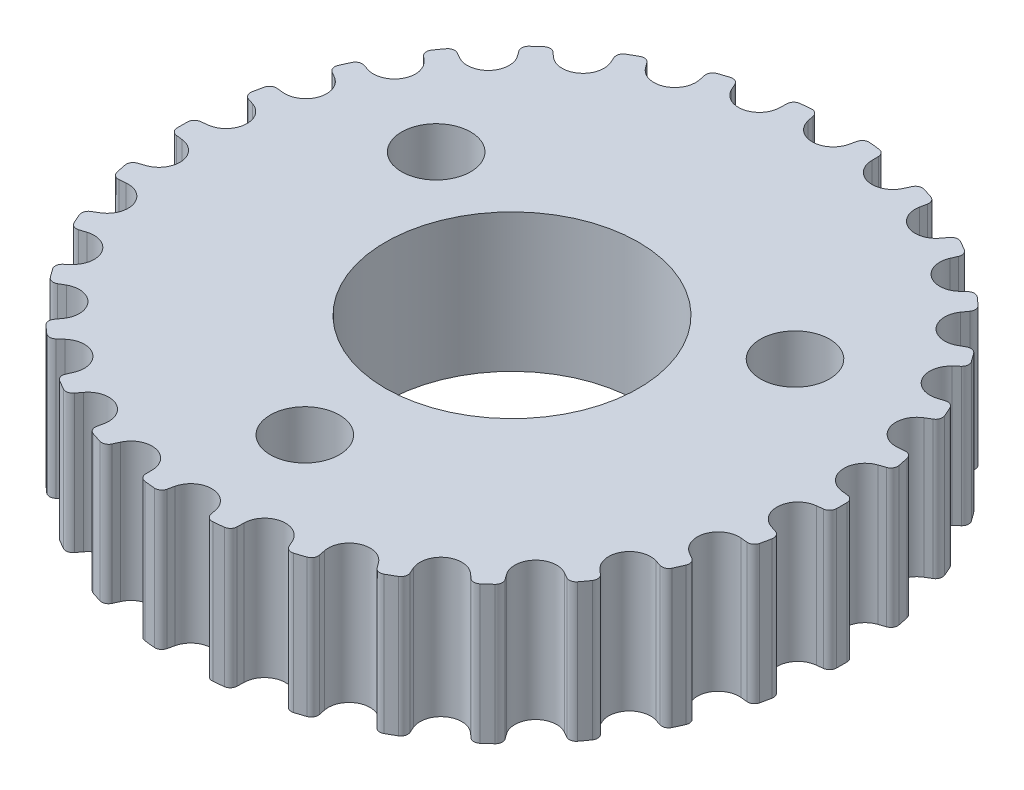
SolidWorks part; units mm, degrees
material "Acrylic (Medium-high impact)"
ref_plane "Front Plane" through (0, 0, 0) normal (0, 0, 1) x (1, 0, 0)
ref_plane "Top Plane" through (0, 0, 0) normal (0, 1, 0) x (1, 0, 0)
ref_plane "Right Plane" through (0, 0, 0) normal (1, 0, 0) x (0, 0, -1)
sketch "Sketch1" plane through (0, 0, 0) normal (0, 1, 0) x (1, 0, 0)
  circle A0 centre (0, 0) radius 14.3239
  dimension "D1" = 28.6479
extrude "Boss-Extrude1" add sketch "Sketch1" along normal blind 6
sketch "Sketch2" plane through (0, 6, 0) normal (0, 1, 0) x (1, 0, 0)
  line L0 (0, 0) -> (0, 14.3239) construction
  line L1 (-0.8883, 13.7564) -> (-0.95, 14.0339)
  line L2 (-2.9781, 14.0109) -> (-2.9781, 14.3239)
  line L3 (-2.9781, 14.3239) -> (2.9781, 14.3239)
  line L4 (0.8883, 13.7564) -> (0.95, 14.0339)
  line L5 (2.9781, 14.0109) -> (2.9781, 14.3239)
  circle A0 centre (0, 0) radius 14.3239 construction
  arc A1 (0.8883, 13.7564) -> (-0.8883, 13.7564) centre (0, 13.9539) cw
  arc A2 (-0.95, 14.0339) -> (-1.2694, 14.2676) centre (-1.2428, 13.9688) ccw
  arc A4 (0.95, 14.0339) -> (1.2694, 14.2676) centre (1.2428, 13.9688) cw
  arc A5 (-1.2694, 14.2676) -> (-2.9781, 14.0109) centre (0, 0) ccw
  arc A6 (1.2694, 14.2676) -> (2.9781, 14.0109) centre (0, 0) cw
  circle A8 centre (0, 0) radius 14.3239 construction
  point P11 (0, 14.3239)
  point P19 (0, 13.0439)
  dimension "D3" = 0.3
  dimension "D5" = 0.91
  dimension "D2" = 0.95
  dimension "D4" = 1.28
  dimension "D6" = 12
extrude "Cut-Extrude1" cut sketch "Sketch2" against normal through all
pattern_circular "CirPattern1" count 30 over 360 about axis through (0, 6, 0) along (0, -1, 0) of "Cut-Extrude1"
sketch "Sketch3" plane through (0, 0, 0) normal (0, -1, 0) x (1, 0, 0)
  circle A0 centre (0, 0) radius 5.5
  dimension "D1" = 11
extrude "Cut-Extrude2" cut sketch "Sketch3" against normal through all
sketch "Sketch4" plane through (0, 0, 0) normal (0, -1, 0) x (1, 0, 0)
  line L0 (0, 0) -> (0, 9) construction
  circle A0 centre (0, 9) radius 1.5
  circle A1 centre (7.7942, -4.5) radius 1.5
  circle A2 centre (-7.7942, -4.5) radius 1.5
  point P14 (0, 0)
  dimension "D1" = 3
  dimension "D2" = 9
  dimension "D3" = 3
extrude "Cut-Extrude3" cut sketch "Sketch4" against normal through all
sketch "Sketch5" plane through (0, 0, 0) normal (0, -1, 0) x (1, 0, 0)
  line L60 (8.7383, -10.682) -> (8.9513, -10.8702)
  line L61 (8.7383, -10.682) -> (8.9513, -10.8702)
  line L62 (9.875, -10.0385) -> (9.7101, -9.807)
  line L63 (9.875, -10.0385) -> (9.7101, -9.807)
  line L64 (12.5987, 6.2896) -> (12.3276, 6.2043)
  line L65 (12.5987, 6.2896) -> (12.3276, 6.2043)
  line L66 (11.5369, 7.5738) -> (11.7463, 7.766)
  line L67 (11.5369, 7.5738) -> (11.7463, 7.766)
  line L68 (-3.638, 13.3126) -> (-3.7561, 13.5712)
  line L69 (-3.638, 13.3126) -> (-3.7561, 13.5712)
  line L70 (-4.9382, 13.1871) -> (-4.8817, 12.9085)
  line L71 (-4.9382, 13.1871) -> (-4.8817, 12.9085)
  line L72 (-11.7463, 7.766) -> (-11.5369, 7.5738)
  line L73 (-11.7463, 7.766) -> (-11.5369, 7.5738)
  line L74 (-12.3276, 6.2043) -> (-12.5987, 6.2896)
  line L75 (-12.3276, 6.2043) -> (-12.5987, 6.2896)
  line L76 (-13.1043, 5.1541) -> (-12.8594, 5.0097)
  line L77 (-13.1043, 5.1541) -> (-12.8594, 5.0097)
  line L78 (-13.3481, 3.5057) -> (-13.6311, 3.5327)
  line L79 (-13.3481, 3.5057) -> (-13.6311, 3.5327)
  line L80 (-13.8895, 2.3169) -> (-13.62, 2.2266)
  line L81 (-13.8895, 2.3169) -> (-13.62, 2.2266)
  line L82 (-13.7853, 0.6538) -> (-14.0677, 0.6215)
  line L83 (-13.7853, 0.6538) -> (-14.0677, 0.6215)
  line L84 (-14.0677, -0.6215) -> (-13.7853, -0.6538)
  line L85 (-14.0677, -0.6215) -> (-13.7853, -0.6538)
  line L86 (-13.62, -2.2266) -> (-13.8895, -2.3169)
  line L87 (-13.62, -2.2266) -> (-13.8895, -2.3169)
  line L88 (-13.6311, -3.5327) -> (-13.3481, -3.5057)
  line L89 (-13.6311, -3.5327) -> (-13.3481, -3.5057)
  line L90 (-12.8594, -5.0097) -> (-13.1043, -5.1541)
  line L91 (-12.8594, -5.0097) -> (-13.1043, -5.1541)
  line L92 (-12.5987, -6.2896) -> (-12.3276, -6.2043)
  line L93 (-12.5987, -6.2896) -> (-12.3276, -6.2043)
  line L94 (-11.5369, -7.5738) -> (-11.7463, -7.766)
  line L95 (-11.5369, -7.5738) -> (-11.7463, -7.766)
  line L96 (-11.0157, -8.7716) -> (-10.7682, -8.6318)
  line L97 (-11.0157, -8.7716) -> (-10.7682, -8.6318)
  line L98 (-9.7101, -9.807) -> (-9.875, -10.0385)
  line L99 (-9.7101, -9.807) -> (-9.875, -10.0385)
  line L100 (-8.9513, -10.8702) -> (-8.7383, -10.682)
  line L101 (-8.9513, -10.8702) -> (-8.7383, -10.682)
  line L102 (-7.4589, -11.6115) -> (-7.5721, -11.8722)
  line L103 (-7.4589, -11.6115) -> (-7.5721, -11.8722)
  line L104 (-6.4956, -12.4937) -> (-6.3264, -12.2653)
  line L105 (-6.4956, -12.4937) -> (-6.3264, -12.2653)
  line L106 (-4.8817, -12.9085) -> (-4.9382, -13.1871)
  line L107 (-4.8817, -12.9085) -> (-4.9382, -13.1871)
  line L108 (-3.7561, -13.5712) -> (-3.638, -13.3126)
  line L109 (-3.7561, -13.5712) -> (-3.638, -13.3126)
  line L110 (-2.0912, -13.6414) -> (-2.0886, -13.9257)
  line L111 (-2.0912, -13.6414) -> (-2.0886, -13.9257)
  line L120 (6.3264, -12.2653) -> (6.4956, -12.4937)
  line L121 (7.5721, -11.8722) -> (7.4589, -11.6115)
  line L124 (10.7682, -8.6318) -> (11.0157, -8.7716)
  line L125 (11.7463, -7.766) -> (11.5369, -7.5738)
  line L126 (12.3276, -6.2043) -> (12.5987, -6.2896)
  line L127 (13.1043, -5.1541) -> (12.8594, -5.0097)
  line L128 (13.3481, -3.5057) -> (13.6311, -3.5327)
  line L129 (13.8895, -2.3169) -> (13.62, -2.2266)
  line L130 (13.7853, -0.6538) -> (14.0677, -0.6215)
  line L131 (14.0677, 0.6215) -> (13.7853, 0.6538)
  line L132 (13.62, 2.2266) -> (13.8895, 2.3169)
  line L133 (13.6311, 3.5327) -> (13.3481, 3.5057)
  line L134 (12.8594, 5.0097) -> (13.1043, 5.1541)
  line L137 (11.0157, 8.7716) -> (10.7682, 8.6318)
  line L138 (9.7101, 9.807) -> (9.875, 10.0385)
  line L139 (8.9513, 10.8702) -> (8.7383, 10.682)
  line L140 (7.4589, 11.6115) -> (7.5721, 11.8722)
  line L141 (6.4956, 12.4937) -> (6.3264, 12.2653)
  line L142 (4.8817, 12.9085) -> (4.9382, 13.1871)
  line L143 (3.7561, 13.5712) -> (3.638, 13.3126)
  line L144 (2.0912, 13.6414) -> (2.0886, 13.9257)
  line L145 (0.8524, 14.0556) -> (0.7907, 13.7781)
  line L146 (-0.7907, 13.7781) -> (-0.8524, 14.0556)
  line L147 (-2.0886, 13.9257) -> (-2.0912, 13.6414)
  line L150 (-6.3264, 12.2653) -> (-6.4956, 12.4937)
  line L151 (-7.5721, 11.8722) -> (-7.4589, 11.6115)
  line L152 (-8.7383, 10.682) -> (-8.9513, 10.8702)
  line L153 (-9.875, 10.0385) -> (-9.7101, 9.807)
  line L154 (-10.7682, 8.6318) -> (-11.0157, 8.7716)
  line L175 (-0.8524, -14.0556) -> (-0.7907, -13.7781)
  line L176 (0.7907, -13.7781) -> (0.8524, -14.0556)
  line L177 (2.0886, -13.9257) -> (2.0912, -13.6414)
  line L178 (3.638, -13.3126) -> (3.7561, -13.5712)
  line L179 (4.9382, -13.1871) -> (4.8817, -12.9085)
  line L180 (6.3264, -12.2653) -> (6.4956, -12.4937)
  line L181 (7.5721, -11.8722) -> (7.4589, -11.6115)
  line L184 (10.7682, -8.6318) -> (11.0157, -8.7716)
  line L185 (11.7463, -7.766) -> (11.5369, -7.5738)
  line L186 (12.3276, -6.2043) -> (12.5987, -6.2896)
  line L187 (13.1043, -5.1541) -> (12.8594, -5.0097)
  line L188 (13.3481, -3.5057) -> (13.6311, -3.5327)
  line L189 (13.8895, -2.3169) -> (13.62, -2.2266)
  line L190 (13.7853, -0.6538) -> (14.0677, -0.6215)
  line L191 (14.0677, 0.6215) -> (13.7853, 0.6538)
  line L192 (13.62, 2.2266) -> (13.8895, 2.3169)
  line L193 (13.6311, 3.5327) -> (13.3481, 3.5057)
  line L194 (12.8594, 5.0097) -> (13.1043, 5.1541)
  line L197 (11.0157, 8.7716) -> (10.7682, 8.6318)
  line L198 (9.7101, 9.807) -> (9.875, 10.0385)
  line L199 (8.9513, 10.8702) -> (8.7383, 10.682)
  line L200 (7.4589, 11.6115) -> (7.5721, 11.8722)
  line L201 (6.4956, 12.4937) -> (6.3264, 12.2653)
  line L202 (4.8817, 12.9085) -> (4.9382, 13.1871)
  line L203 (3.7561, 13.5712) -> (3.638, 13.3126)
  line L204 (2.0912, 13.6414) -> (2.0886, 13.9257)
  line L205 (0.8524, 14.0556) -> (0.7907, 13.7781)
  line L206 (-0.7907, 13.7781) -> (-0.8524, 14.0556)
  line L207 (-2.0886, 13.9257) -> (-2.0912, 13.6414)
  line L210 (-6.3264, 12.2653) -> (-6.4956, 12.4937)
  line L211 (-7.5721, 11.8722) -> (-7.4589, 11.6115)
  line L212 (-8.7383, 10.682) -> (-8.9513, 10.8702)
  line L213 (-9.875, 10.0385) -> (-9.7101, 9.807)
  line L214 (-10.7682, 8.6318) -> (-11.0157, 8.7716)
  line L235 (-0.8524, -14.0556) -> (-0.7907, -13.7781)
  line L236 (0.7907, -13.7781) -> (0.8524, -14.0556)
  line L237 (2.0886, -13.9257) -> (2.0912, -13.6414)
  line L238 (3.638, -13.3126) -> (3.7561, -13.5712)
  line L239 (4.9382, -13.1871) -> (4.8817, -12.9085)
  arc A76 (8.9513, -10.8702) -> (9.479, -10.8719) centre (9.2161, -10.5704) ccw
  arc A77 (8.9513, -10.8702) -> (9.479, -10.8719) centre (9.2161, -10.5704) ccw
  arc A78 (9.479, -10.8719) -> (9.8216, -10.5635) centre (0, 0) ccw
  arc A79 (9.479, -10.8719) -> (9.8216, -10.5635) centre (0, 0) ccw
  arc A80 (9.8216, -10.5635) -> (9.875, -10.0385) centre (9.5492, -10.2705) ccw
  arc A81 (9.8216, -10.5635) -> (9.875, -10.0385) centre (9.5492, -10.2705) ccw
  circle A120 centre (0, 0) radius 13.0439
  arc A121 (-0.8883, 13.7564) -> (0.8883, 13.7564) centre (0, 13.9539) ccw construction
  arc A128 (11.5369, 7.5738) -> (12.3276, 6.2043) centre (12.0845, 6.977) ccw
  arc A129 (11.5369, 7.5738) -> (12.3276, 6.2043) centre (12.0845, 6.977) ccw
  arc A130 (-3.7561, 13.5712) -> (-4.2375, 13.7875) centre (-4.12, 13.4051) ccw
  arc A131 (-3.7561, 13.5712) -> (-4.2375, 13.7875) centre (-4.12, 13.4051) ccw
  arc A132 (-4.2375, 13.7875) -> (-4.6759, 13.645) centre (0, 0) ccw
  arc A133 (-4.2375, 13.7875) -> (-4.6759, 13.645) centre (0, 0) ccw
  arc A134 (-4.6759, 13.645) -> (-4.9382, 13.1871) centre (-4.5462, 13.2666) ccw
  arc A135 (-4.6759, 13.645) -> (-4.9382, 13.1871) centre (-4.5462, 13.2666) ccw
  arc A136 (-11.8032, 8.2906) -> (-11.7463, 7.766) centre (-11.4759, 8.0607) ccw
  arc A137 (-11.8032, 8.2906) -> (-11.7463, 7.766) centre (-11.4759, 8.0607) ccw
  arc A138 (-12.3276, 6.2043) -> (-11.5369, 7.5738) centre (-12.0845, 6.977) ccw
  arc A139 (-12.3276, 6.2043) -> (-11.5369, 7.5738) centre (-12.0845, 6.977) ccw
  arc A140 (-12.5987, 6.2896) -> (-13.0815, 6.0766) centre (-12.7187, 5.908) ccw
  arc A141 (-12.5987, 6.2896) -> (-13.0815, 6.0766) centre (-12.7187, 5.908) ccw
  arc A142 (-13.0815, 6.0766) -> (-13.269, 5.6554) centre (0, 0) ccw
  arc A143 (-13.0815, 6.0766) -> (-13.269, 5.6554) centre (0, 0) ccw
  arc A144 (-13.269, 5.6554) -> (-13.1043, 5.1541) centre (-12.901, 5.4986) ccw
  arc A145 (-13.269, 5.6554) -> (-13.1043, 5.1541) centre (-12.901, 5.4986) ccw
  arc A146 (-13.3481, 3.5057) -> (-12.8594, 5.0097) centre (-13.271, 4.312) ccw
  arc A147 (-13.3481, 3.5057) -> (-12.8594, 5.0097) centre (-13.271, 4.312) ccw
  arc A148 (-13.6311, 3.5327) -> (-14.059, 3.224) centre (-13.6691, 3.1346) ccw
  arc A149 (-13.6311, 3.5327) -> (-14.059, 3.224) centre (-13.6691, 3.1346) ccw
  arc A150 (-14.059, 3.224) -> (-14.1549, 2.7731) centre (0, 0) ccw
  arc A151 (-14.059, 3.224) -> (-14.1549, 2.7731) centre (0, 0) ccw
  arc A152 (-14.1549, 2.7731) -> (-13.8895, 2.3169) centre (-13.7623, 2.6962) ccw
  arc A153 (-14.1549, 2.7731) -> (-13.8895, 2.3169) centre (-13.7623, 2.6962) ccw
  arc A154 (-13.7853, 0.6538) -> (-13.62, 2.2266) centre (-13.8775, 1.4586) ccw
  arc A155 (-13.7853, 0.6538) -> (-13.62, 2.2266) centre (-13.8775, 1.4586) ccw
  arc A156 (-14.0677, 0.6215) -> (-14.4221, 0.2305) centre (-14.0222, 0.2241) ccw
  arc A157 (-14.0677, 0.6215) -> (-14.4221, 0.2305) centre (-14.0222, 0.2241) ccw
  arc A158 (-14.4221, 0.2305) -> (-14.4221, -0.2305) centre (0, 0) ccw
  arc A159 (-14.4221, 0.2305) -> (-14.4221, -0.2305) centre (0, 0) ccw
  arc A160 (-14.4221, -0.2305) -> (-14.0677, -0.6215) centre (-14.0222, -0.2241) ccw
  arc A161 (-14.4221, -0.2305) -> (-14.0677, -0.6215) centre (-14.0222, -0.2241) ccw
  arc A162 (-13.62, -2.2266) -> (-13.7853, -0.6538) centre (-13.8775, -1.4586) ccw
  arc A163 (-13.62, -2.2266) -> (-13.7853, -0.6538) centre (-13.8775, -1.4586) ccw
  arc A164 (-13.8895, -2.3169) -> (-14.1549, -2.7731) centre (-13.7623, -2.6962) ccw
  arc A165 (-13.8895, -2.3169) -> (-14.1549, -2.7731) centre (-13.7623, -2.6962) ccw
  arc A166 (-14.1549, -2.7731) -> (-14.059, -3.224) centre (0, 0) ccw
  arc A167 (-14.1549, -2.7731) -> (-14.059, -3.224) centre (0, 0) ccw
  arc A168 (-14.059, -3.224) -> (-13.6311, -3.5327) centre (-13.6691, -3.1346) ccw
  arc A169 (-14.059, -3.224) -> (-13.6311, -3.5327) centre (-13.6691, -3.1346) ccw
  arc A170 (-12.8594, -5.0097) -> (-13.3481, -3.5057) centre (-13.271, -4.312) ccw
  arc A171 (-12.8594, -5.0097) -> (-13.3481, -3.5057) centre (-13.271, -4.312) ccw
  arc A172 (-13.1043, -5.1541) -> (-13.269, -5.6554) centre (-12.901, -5.4986) ccw
  arc A173 (-13.1043, -5.1541) -> (-13.269, -5.6554) centre (-12.901, -5.4986) ccw
  arc A174 (-13.269, -5.6554) -> (-13.0815, -6.0766) centre (0, 0) ccw
  arc A175 (-13.269, -5.6554) -> (-13.0815, -6.0766) centre (0, 0) ccw
  arc A176 (-13.0815, -6.0766) -> (-12.5987, -6.2896) centre (-12.7187, -5.908) ccw
  arc A177 (-13.0815, -6.0766) -> (-12.5987, -6.2896) centre (-12.7187, -5.908) ccw
  arc A178 (-11.5369, -7.5738) -> (-12.3276, -6.2043) centre (-12.0845, -6.977) ccw
  arc A179 (-11.5369, -7.5738) -> (-12.3276, -6.2043) centre (-12.0845, -6.977) ccw
  arc A180 (-11.7463, -7.766) -> (-11.8032, -8.2906) centre (-11.4759, -8.0607) ccw
  arc A181 (-11.7463, -7.766) -> (-11.8032, -8.2906) centre (-11.4759, -8.0607) ccw
  arc A182 (-11.8032, -8.2906) -> (-11.5323, -8.6636) centre (0, 0) ccw
  arc A183 (-11.8032, -8.2906) -> (-11.5323, -8.6636) centre (0, 0) ccw
  arc A184 (-11.5323, -8.6636) -> (-11.0157, -8.7716) centre (-11.2124, -8.4233) ccw
  arc A185 (-11.5323, -8.6636) -> (-11.0157, -8.7716) centre (-11.2124, -8.4233) ccw
  arc A186 (-9.7101, -9.807) -> (-10.7682, -8.6318) centre (-10.3698, -9.337) ccw
  arc A187 (-9.7101, -9.807) -> (-10.7682, -8.6318) centre (-10.3698, -9.337) ccw
  arc A188 (-9.875, -10.0385) -> (-9.8216, -10.5635) centre (-9.5492, -10.2705) ccw
  arc A189 (-9.875, -10.0385) -> (-9.8216, -10.5635) centre (-9.5492, -10.2705) ccw
  arc A190 (-9.8216, -10.5635) -> (-9.479, -10.8719) centre (0, 0) ccw
  arc A191 (-9.8216, -10.5635) -> (-9.479, -10.8719) centre (0, 0) ccw
  arc A192 (-9.479, -10.8719) -> (-8.9513, -10.8702) centre (-9.2161, -10.5704) ccw
  arc A193 (-9.479, -10.8719) -> (-8.9513, -10.8702) centre (-9.2161, -10.5704) ccw
  arc A194 (-7.4589, -11.6115) -> (-8.7383, -10.682) centre (-8.2019, -11.289) ccw
  arc A195 (-7.4589, -11.6115) -> (-8.7383, -10.682) centre (-8.2019, -11.289) ccw
  arc A196 (-7.5721, -11.8722) -> (-7.4107, -12.3747) centre (-7.2051, -12.0315) ccw
  arc A197 (-7.5721, -11.8722) -> (-7.4107, -12.3747) centre (-7.2051, -12.0315) ccw
  arc A198 (-7.4107, -12.3747) -> (-7.0114, -12.6052) centre (0, 0) ccw
  arc A199 (-7.4107, -12.3747) -> (-7.0114, -12.6052) centre (0, 0) ccw
  arc A200 (-7.0114, -12.6052) -> (-6.4956, -12.4937) centre (-6.817, -12.2556) ccw
  arc A201 (-7.0114, -12.6052) -> (-6.4956, -12.4937) centre (-6.817, -12.2556) ccw
  arc A202 (-4.8817, -12.9085) -> (-6.3264, -12.2653) centre (-5.6756, -12.7476) ccw
  arc A203 (-4.8817, -12.9085) -> (-6.3264, -12.2653) centre (-5.6756, -12.7476) ccw
  arc A204 (-4.9382, -13.1871) -> (-4.6759, -13.645) centre (-4.5462, -13.2666) ccw
  arc A205 (-4.9382, -13.1871) -> (-4.6759, -13.645) centre (-4.5462, -13.2666) ccw
  arc A206 (-4.6759, -13.645) -> (-4.2375, -13.7875) centre (0, 0) ccw
  arc A207 (-4.6759, -13.645) -> (-4.2375, -13.7875) centre (0, 0) ccw
  arc A208 (-4.2375, -13.7875) -> (-3.7561, -13.5712) centre (-4.12, -13.4051) ccw
  arc A209 (-4.2375, -13.7875) -> (-3.7561, -13.5712) centre (-4.12, -13.4051) ccw
  arc A210 (-2.0912, -13.6414) -> (-3.638, -13.3126) centre (-2.9012, -13.649) ccw
  arc A211 (-2.0912, -13.6414) -> (-3.638, -13.3126) centre (-2.9012, -13.649) ccw
  arc A212 (-2.0886, -13.9257) -> (-1.7367, -14.319) centre (-1.6886, -13.9219) ccw
  arc A213 (-2.0886, -13.9257) -> (-1.7367, -14.319) centre (-1.6886, -13.9219) ccw
  arc A214 (-1.7367, -14.319) -> (-1.2783, -14.3672) centre (0, 0) ccw
  arc A215 (-1.7367, -14.319) -> (-1.2783, -14.3672) centre (0, 0) ccw
  arc A240 (6.4956, -12.4937) -> (7.0114, -12.6052) centre (6.817, -12.2556) ccw
  arc A241 (7.0114, -12.6052) -> (7.4107, -12.3747) centre (0, 0) ccw
  arc A242 (7.4107, -12.3747) -> (7.5721, -11.8722) centre (7.2051, -12.0315) ccw
  arc A243 (8.7383, -10.682) -> (7.4589, -11.6115) centre (8.2019, -11.289) ccw
  arc A247 (10.7682, -8.6318) -> (9.7101, -9.807) centre (10.3698, -9.337) ccw
  arc A248 (11.0157, -8.7716) -> (11.5323, -8.6636) centre (11.2124, -8.4233) ccw
  arc A249 (11.5323, -8.6636) -> (11.8032, -8.2906) centre (0, 0) ccw
  arc A250 (11.8032, -8.2906) -> (11.7463, -7.766) centre (11.4759, -8.0607) ccw
  arc A251 (12.3276, -6.2043) -> (11.5369, -7.5738) centre (12.0845, -6.977) ccw
  arc A252 (12.5987, -6.2896) -> (13.0815, -6.0766) centre (12.7187, -5.908) ccw
  arc A253 (13.0815, -6.0766) -> (13.269, -5.6554) centre (0, 0) ccw
  arc A254 (13.269, -5.6554) -> (13.1043, -5.1541) centre (12.901, -5.4986) ccw
  arc A255 (13.3481, -3.5057) -> (12.8594, -5.0097) centre (13.271, -4.312) ccw
  arc A256 (13.6311, -3.5327) -> (14.059, -3.224) centre (13.6691, -3.1346) ccw
  arc A257 (14.059, -3.224) -> (14.1549, -2.7731) centre (0, 0) ccw
  arc A258 (14.1549, -2.7731) -> (13.8895, -2.3169) centre (13.7623, -2.6962) ccw
  arc A259 (13.7853, -0.6538) -> (13.62, -2.2266) centre (13.8775, -1.4586) ccw
  arc A260 (14.0677, -0.6215) -> (14.4221, -0.2305) centre (14.0222, -0.2241) ccw
  arc A261 (14.4221, -0.2305) -> (14.4221, 0.2305) centre (0, 0) ccw
  arc A262 (14.4221, 0.2305) -> (14.0677, 0.6215) centre (14.0222, 0.2241) ccw
  arc A263 (13.62, 2.2266) -> (13.7853, 0.6538) centre (13.8775, 1.4586) ccw
  arc A264 (13.8895, 2.3169) -> (14.1549, 2.7731) centre (13.7623, 2.6962) ccw
  arc A265 (14.1549, 2.7731) -> (14.059, 3.224) centre (0, 0) ccw
  arc A266 (14.059, 3.224) -> (13.6311, 3.5327) centre (13.6691, 3.1346) ccw
  arc A267 (12.8594, 5.0097) -> (13.3481, 3.5057) centre (13.271, 4.312) ccw
  arc A268 (13.1043, 5.1541) -> (13.269, 5.6554) centre (12.901, 5.4986) ccw
  arc A269 (13.269, 5.6554) -> (13.0815, 6.0766) centre (0, 0) ccw
  arc A270 (13.0815, 6.0766) -> (12.5987, 6.2896) centre (12.7187, 5.908) ccw
  arc A272 (11.7463, 7.766) -> (11.8032, 8.2906) centre (11.4759, 8.0607) ccw
  arc A273 (11.8032, 8.2906) -> (11.5323, 8.6636) centre (0, 0) ccw
  arc A274 (11.5323, 8.6636) -> (11.0157, 8.7716) centre (11.2124, 8.4233) ccw
  arc A275 (9.7101, 9.807) -> (10.7682, 8.6318) centre (10.3698, 9.337) ccw
  arc A276 (9.875, 10.0385) -> (9.8216, 10.5635) centre (9.5492, 10.2705) ccw
  arc A277 (9.8216, 10.5635) -> (9.479, 10.8719) centre (0, 0) ccw
  arc A278 (9.479, 10.8719) -> (8.9513, 10.8702) centre (9.2161, 10.5704) ccw
  arc A279 (7.4589, 11.6115) -> (8.7383, 10.682) centre (8.2019, 11.289) ccw
  arc A280 (7.5721, 11.8722) -> (7.4107, 12.3747) centre (7.2051, 12.0315) ccw
  arc A281 (7.4107, 12.3747) -> (7.0114, 12.6052) centre (0, 0) ccw
  arc A282 (7.0114, 12.6052) -> (6.4956, 12.4937) centre (6.817, 12.2556) ccw
  arc A283 (4.8817, 12.9085) -> (6.3264, 12.2653) centre (5.6756, 12.7476) ccw
  arc A284 (4.9382, 13.1871) -> (4.6759, 13.645) centre (4.5462, 13.2666) ccw
  arc A285 (4.6759, 13.645) -> (4.2375, 13.7875) centre (0, 0) ccw
  arc A286 (4.2375, 13.7875) -> (3.7561, 13.5712) centre (4.12, 13.4051) ccw
  arc A287 (2.0912, 13.6414) -> (3.638, 13.3126) centre (2.9012, 13.649) ccw
  arc A288 (2.0886, 13.9257) -> (1.7367, 14.319) centre (1.6886, 13.9219) ccw
  arc A289 (1.7367, 14.319) -> (1.2783, 14.3672) centre (0, 0) ccw
  arc A290 (1.2783, 14.3672) -> (0.8524, 14.0556) centre (1.2428, 13.9688) ccw
  arc A291 (-0.7907, 13.7781) -> (0.7907, 13.7781) centre (0, 13.9539) ccw
  arc A292 (-0.8524, 14.0556) -> (-1.2783, 14.3672) centre (-1.2428, 13.9688) ccw
  arc A293 (-1.2783, 14.3672) -> (-1.7367, 14.319) centre (0, 0) ccw
  arc A294 (-1.7367, 14.319) -> (-2.0886, 13.9257) centre (-1.6886, 13.9219) ccw
  arc A295 (-3.638, 13.3126) -> (-2.0912, 13.6414) centre (-2.9012, 13.649) ccw
  arc A299 (-6.3264, 12.2653) -> (-4.8817, 12.9085) centre (-5.6756, 12.7476) ccw
  arc A300 (-6.4956, 12.4937) -> (-7.0114, 12.6052) centre (-6.817, 12.2556) ccw
  arc A301 (-7.0114, 12.6052) -> (-7.4107, 12.3747) centre (0, 0) ccw
  arc A302 (-7.4107, 12.3747) -> (-7.5721, 11.8722) centre (-7.2051, 12.0315) ccw
  arc A303 (-8.7383, 10.682) -> (-7.4589, 11.6115) centre (-8.2019, 11.289) ccw
  arc A304 (-8.9513, 10.8702) -> (-9.479, 10.8719) centre (-9.2161, 10.5704) ccw
  arc A305 (-9.479, 10.8719) -> (-9.8216, 10.5635) centre (0, 0) ccw
  arc A306 (-9.8216, 10.5635) -> (-9.875, 10.0385) centre (-9.5492, 10.2705) ccw
  arc A307 (-10.7682, 8.6318) -> (-9.7101, 9.807) centre (-10.3698, 9.337) ccw
  arc A308 (-11.0157, 8.7716) -> (-11.5323, 8.6636) centre (-11.2124, 8.4233) ccw
  arc A309 (-11.5323, 8.6636) -> (-11.8032, 8.2906) centre (0, 0) ccw
  arc A350 (-1.2783, -14.3672) -> (-0.8524, -14.0556) centre (-1.2428, -13.9688) ccw
  arc A351 (0.7907, -13.7781) -> (-0.7907, -13.7781) centre (0, -13.9539) ccw
  arc A352 (0.8524, -14.0556) -> (1.2783, -14.3672) centre (1.2428, -13.9688) ccw
  arc A353 (1.2783, -14.3672) -> (1.7367, -14.319) centre (0, 0) ccw
  arc A354 (1.7367, -14.319) -> (2.0886, -13.9257) centre (1.6886, -13.9219) ccw
  arc A355 (3.638, -13.3126) -> (2.0912, -13.6414) centre (2.9012, -13.649) ccw
  arc A356 (3.7561, -13.5712) -> (4.2375, -13.7875) centre (4.12, -13.4051) ccw
  arc A357 (4.2375, -13.7875) -> (4.6759, -13.645) centre (0, 0) ccw
  arc A358 (4.6759, -13.645) -> (4.9382, -13.1871) centre (4.5462, -13.2666) ccw
  arc A359 (6.3264, -12.2653) -> (4.8817, -12.9085) centre (5.6756, -12.7476) ccw
  arc A360 (6.4956, -12.4937) -> (7.0114, -12.6052) centre (6.817, -12.2556) ccw
  arc A361 (7.0114, -12.6052) -> (7.4107, -12.3747) centre (0, 0) ccw
  arc A362 (7.4107, -12.3747) -> (7.5721, -11.8722) centre (7.2051, -12.0315) ccw
  arc A363 (8.7383, -10.682) -> (7.4589, -11.6115) centre (8.2019, -11.289) ccw
  arc A367 (10.7682, -8.6318) -> (9.7101, -9.807) centre (10.3698, -9.337) ccw
  arc A368 (11.0157, -8.7716) -> (11.5323, -8.6636) centre (11.2124, -8.4233) ccw
  arc A369 (11.5323, -8.6636) -> (11.8032, -8.2906) centre (0, 0) ccw
  arc A370 (11.8032, -8.2906) -> (11.7463, -7.766) centre (11.4759, -8.0607) ccw
  arc A371 (12.3276, -6.2043) -> (11.5369, -7.5738) centre (12.0845, -6.977) ccw
  arc A372 (12.5987, -6.2896) -> (13.0815, -6.0766) centre (12.7187, -5.908) ccw
  arc A373 (13.0815, -6.0766) -> (13.269, -5.6554) centre (0, 0) ccw
  arc A374 (13.269, -5.6554) -> (13.1043, -5.1541) centre (12.901, -5.4986) ccw
  arc A375 (13.3481, -3.5057) -> (12.8594, -5.0097) centre (13.271, -4.312) ccw
  arc A376 (13.6311, -3.5327) -> (14.059, -3.224) centre (13.6691, -3.1346) ccw
  arc A377 (14.059, -3.224) -> (14.1549, -2.7731) centre (0, 0) ccw
  arc A378 (14.1549, -2.7731) -> (13.8895, -2.3169) centre (13.7623, -2.6962) ccw
  arc A379 (13.7853, -0.6538) -> (13.62, -2.2266) centre (13.8775, -1.4586) ccw
  arc A380 (14.0677, -0.6215) -> (14.4221, -0.2305) centre (14.0222, -0.2241) ccw
  arc A381 (14.4221, -0.2305) -> (14.4221, 0.2305) centre (0, 0) ccw
  arc A382 (14.4221, 0.2305) -> (14.0677, 0.6215) centre (14.0222, 0.2241) ccw
  arc A383 (13.62, 2.2266) -> (13.7853, 0.6538) centre (13.8775, 1.4586) ccw
  arc A384 (13.8895, 2.3169) -> (14.1549, 2.7731) centre (13.7623, 2.6962) ccw
  arc A385 (14.1549, 2.7731) -> (14.059, 3.224) centre (0, 0) ccw
  arc A386 (14.059, 3.224) -> (13.6311, 3.5327) centre (13.6691, 3.1346) ccw
  arc A387 (12.8594, 5.0097) -> (13.3481, 3.5057) centre (13.271, 4.312) ccw
  arc A388 (13.1043, 5.1541) -> (13.269, 5.6554) centre (12.901, 5.4986) ccw
  arc A389 (13.269, 5.6554) -> (13.0815, 6.0766) centre (0, 0) ccw
  arc A390 (13.0815, 6.0766) -> (12.5987, 6.2896) centre (12.7187, 5.908) ccw
  arc A392 (11.7463, 7.766) -> (11.8032, 8.2906) centre (11.4759, 8.0607) ccw
  arc A393 (11.8032, 8.2906) -> (11.5323, 8.6636) centre (0, 0) ccw
  arc A394 (11.5323, 8.6636) -> (11.0157, 8.7716) centre (11.2124, 8.4233) ccw
  arc A395 (9.7101, 9.807) -> (10.7682, 8.6318) centre (10.3698, 9.337) ccw
  arc A396 (9.875, 10.0385) -> (9.8216, 10.5635) centre (9.5492, 10.2705) ccw
  arc A397 (9.8216, 10.5635) -> (9.479, 10.8719) centre (0, 0) ccw
  arc A398 (9.479, 10.8719) -> (8.9513, 10.8702) centre (9.2161, 10.5704) ccw
  arc A399 (7.4589, 11.6115) -> (8.7383, 10.682) centre (8.2019, 11.289) ccw
  arc A400 (7.5721, 11.8722) -> (7.4107, 12.3747) centre (7.2051, 12.0315) ccw
  arc A401 (7.4107, 12.3747) -> (7.0114, 12.6052) centre (0, 0) ccw
  arc A402 (7.0114, 12.6052) -> (6.4956, 12.4937) centre (6.817, 12.2556) ccw
  arc A403 (4.8817, 12.9085) -> (6.3264, 12.2653) centre (5.6756, 12.7476) ccw
  arc A404 (4.9382, 13.1871) -> (4.6759, 13.645) centre (4.5462, 13.2666) ccw
  arc A405 (4.6759, 13.645) -> (4.2375, 13.7875) centre (0, 0) ccw
  arc A406 (4.2375, 13.7875) -> (3.7561, 13.5712) centre (4.12, 13.4051) ccw
  arc A407 (2.0912, 13.6414) -> (3.638, 13.3126) centre (2.9012, 13.649) ccw
  arc A408 (2.0886, 13.9257) -> (1.7367, 14.319) centre (1.6886, 13.9219) ccw
  arc A409 (1.7367, 14.319) -> (1.2783, 14.3672) centre (0, 0) ccw
  arc A410 (1.2783, 14.3672) -> (0.8524, 14.0556) centre (1.2428, 13.9688) ccw
  arc A411 (-0.7907, 13.7781) -> (0.7907, 13.7781) centre (0, 13.9539) ccw
  arc A412 (-0.8524, 14.0556) -> (-1.2783, 14.3672) centre (-1.2428, 13.9688) ccw
  arc A413 (-1.2783, 14.3672) -> (-1.7367, 14.319) centre (0, 0) ccw
  arc A414 (-1.7367, 14.319) -> (-2.0886, 13.9257) centre (-1.6886, 13.9219) ccw
  arc A415 (-3.638, 13.3126) -> (-2.0912, 13.6414) centre (-2.9012, 13.649) ccw
  arc A419 (-6.3264, 12.2653) -> (-4.8817, 12.9085) centre (-5.6756, 12.7476) ccw
  arc A420 (-6.4956, 12.4937) -> (-7.0114, 12.6052) centre (-6.817, 12.2556) ccw
  arc A421 (-7.0114, 12.6052) -> (-7.4107, 12.3747) centre (0, 0) ccw
  arc A422 (-7.4107, 12.3747) -> (-7.5721, 11.8722) centre (-7.2051, 12.0315) ccw
  arc A423 (-8.7383, 10.682) -> (-7.4589, 11.6115) centre (-8.2019, 11.289) ccw
  arc A424 (-8.9513, 10.8702) -> (-9.479, 10.8719) centre (-9.2161, 10.5704) ccw
  arc A425 (-9.479, 10.8719) -> (-9.8216, 10.5635) centre (0, 0) ccw
  arc A426 (-9.8216, 10.5635) -> (-9.875, 10.0385) centre (-9.5492, 10.2705) ccw
  arc A427 (-10.7682, 8.6318) -> (-9.7101, 9.807) centre (-10.3698, 9.337) ccw
  arc A428 (-11.0157, 8.7716) -> (-11.5323, 8.6636) centre (-11.2124, 8.4233) ccw
  arc A429 (-11.5323, 8.6636) -> (-11.8032, 8.2906) centre (0, 0) ccw
  arc A470 (-1.2783, -14.3672) -> (-0.8524, -14.0556) centre (-1.2428, -13.9688) ccw
  arc A471 (0.7907, -13.7781) -> (-0.7907, -13.7781) centre (0, -13.9539) ccw
  arc A472 (0.8524, -14.0556) -> (1.2783, -14.3672) centre (1.2428, -13.9688) ccw
  arc A473 (1.2783, -14.3672) -> (1.7367, -14.319) centre (0, 0) ccw
  arc A474 (1.7367, -14.319) -> (2.0886, -13.9257) centre (1.6886, -13.9219) ccw
  arc A475 (3.638, -13.3126) -> (2.0912, -13.6414) centre (2.9012, -13.649) ccw
  arc A476 (3.7561, -13.5712) -> (4.2375, -13.7875) centre (4.12, -13.4051) ccw
  arc A477 (4.2375, -13.7875) -> (4.6759, -13.645) centre (0, 0) ccw
  arc A478 (4.6759, -13.645) -> (4.9382, -13.1871) centre (4.5462, -13.2666) ccw
  arc A479 (6.3264, -12.2653) -> (4.8817, -12.9085) centre (5.6756, -12.7476) ccw
  dimension "D1" = 0.1
extrude "Boss-Extrude2" [suppressed] add sketch "Sketch5" against normal up to surface (5.8 mm away) up to face at (7.7942, 6, -6)
equation "\"smallPulleyTeeth\"= 30"
equation "\"largePulleyTeeth\"= 30"
equation "\"eighthThick\"= 3.0mm"
equation "\"D1@Sketch1\"=3*\"largePulleyTeeth\"/pi"
equation "\"D1@Boss-Extrude1\" = \"eighthThick\" * 2"
equation "\"D6@Sketch2\"=360/\"largePulleyTeeth\""
equation "\"quarterThick\"=6.0mm"
equation "\"D1@CirPattern1\"=\"largePulleyTeeth\""
equation "\"sixteenthThick\" = 1.7mm"
equation "\"OD\" = 145mm"
equation "\"puckAngle\" = 60.5deg"
equation "\"puckDiam\" = 76.5mm"
equation "\"axlePress\" = 5.9mm"
equation "\"press\" = 0.2mm"
equation "\"wheelClear\" = 0.3mm"
equation "\"10-32clear\" = 4.8mm"
equation "\"D1@Sketch4\"=\"4-40clear\""
equation "\"6-32clear\" = 3.3mm"
equation "\"8-32clear\" = 4.0mm"
equation "\"4-40clear\" = 3.0mm"
equation "\"wheelHeight\" = 22mm"
equation "\"wheelWell\" = 65mm"
